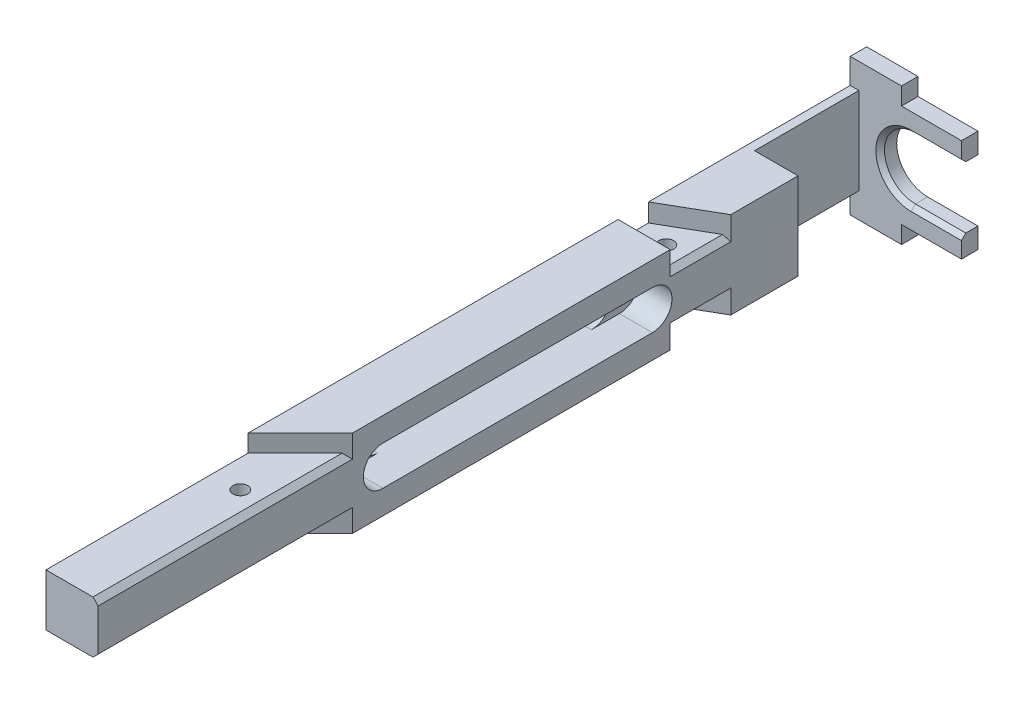
SolidWorks part; units mm, degrees
ref_plane "前视基准面" through (0, 0, 0) normal (0, 0, 1) x (1, 0, 0)
ref_plane "上视基准面" through (0, 0, 0) normal (0, 1, 0) x (1, 0, 0)
ref_plane "右视基准面" through (0, 0, 0) normal (1, 0, 0) x (0, 0, -1)
sketch "草图1" plane through (0, 0, 0) normal (1, 0, 0) x (0, 0, -1)
  line L0 (-15.5, 0) -> (15.5, 0) construction
  line L1 (-25, 5) -> (25, 5)
  line L2 (-25, 5) -> (-25, 3)
  line L3 (-25, -5) -> (25, -5)
  line L4 (25, 5) -> (25, 3)
  line L5 (-25, 5) -> (25, -5) construction
  line L6 (-25, -5) -> (25, 5) construction
  line L7 (-15.5, 2.25) -> (15.5, 2.25)
  line L8 (-15.5, -2.25) -> (15.5, -2.25)
  line L9 (-12.3, 0) -> (12.3, 0) construction
  line L10 (-12.3, 2.25) -> (12.3, 2.25)
  line L11 (-12.3, -2.25) -> (12.3, -2.25)
  line L12 (25, 3) -> (48.25, 3)
  line L13 (-48.25, 3) -> (-25, 3)
  line L14 (-48.25, 3) -> (-48.25, -3)
  line L15 (-48.25, -3) -> (-25, -3)
  line L16 (48.25, 3) -> (48.25, -3)
  line L17 (-48.25, 3) -> (48.25, -3) construction
  line L18 (-48.25, -3) -> (48.25, 3) construction
  line L19 (25, -3) -> (48.25, -3)
  line L20 (-25, -3) -> (-25, -5)
  line L21 (25, -3) -> (25, -5)
  arc A0 (-15.5, 2.25) -> (-15.5, -2.25) centre (-15.5, 0) ccw
  arc A1 (15.5, -2.25) -> (15.5, 2.25) centre (15.5, 0) ccw
  arc A2 (-12.3, 2.25) -> (-12.3, -2.25) centre (-12.3, 0) ccw
  arc A3 (12.3, -2.25) -> (12.3, 2.25) centre (12.3, 0) ccw
  point P0 (0, 0)
  point P8 (0, 0)
  point P14 (0, 0)
  point P20 (0, 0)
  dimension "D1" = 31
  dimension "D2" = 24.6
  dimension "D3" = 4.5
  dimension "D4" = 10
  dimension "D5" = 23.25
  dimension "D6" = 96.5
  dimension "D7" = 6
extrude "凸台-拉伸1" add sketch "草图1" against normal blind 6 contours L2 L13 L14 L15 L20 L3 L21 L19 L16 L12 L4 L1
extrude "切除-拉伸1" cut sketch "草图1<3>" against normal blind 3.8 contours A0 L8 A1 L7
sketch "草图1<3>" plane through (0, 0, 0) normal (1, 0, 0) x (0, 0, -1) same geometry as "草图1"
extrude "切除-拉伸2" cut sketch "草图1<4>" against normal through all contours A2 L11 A3 L10
sketch "草图1<4>" plane through (0, 0, 0) normal (1, 0, 0) x (0, 0, -1) same geometry as "草图1"
sketch "草图3" plane through (0, 0, -48.25) normal (0, 0, -1) x (-1, 0, 0)
  line L1 (-7.6413, 9.5848) -> (10.8952, 9.5848)
  line L2 (-7.6413, 9.5848) -> (-7.6413, -6.0527)
  line L3 (-7.6413, -6.0527) -> (10.8952, -6.0527)
  line L4 (10.8952, 9.5848) -> (10.8952, -6.0527)
extrude "切除-拉伸3" cut sketch "草图3" against normal blind 4
sketch "草图4" plane through (0, 0, -25) normal (0, 0, -1) x (-1, 0, 0)
  line L1 (0, 5) -> (6, 5)
  line L2 (0, 5) -> (0, -5)
  line L3 (0, -5) -> (6, -5)
  line L4 (6, 5) -> (6, -5)
extrude "凸台-拉伸2" add sketch "草图4" along normal up to surface (19.25 mm away) up to face at (-3, 0, -44.25)
sketch "草图5" plane through (0, -5, 0) normal (0, -1, 0) x (1, 0, 0)
  circle A4 centre (-2.8, 29.1) radius 0.85
  circle A5 centre (-2.8, -19.9) radius 0.85
  circle A8 centre (-2.8, -19.9) radius 1.2 construction
  circle A9 centre (-2.8, 29.1) radius 1.2 construction
  dimension "D1" = 1.7
extrude "切除-拉伸4" cut sketch "草图5" against normal through all
sketch "草图7" plane through (0, 0, -44.25) normal (0, 0, -1) x (-1, 0, 0)
  line L0 (6, 5) -> (6, -5) construction
  line L1 (6, 5.9) -> (-6.8, 5.9)
  line L2 (6, 5.9) -> (6, -5.9)
  line L3 (6, -5.9) -> (-6.8, -5.9)
  line L4 (-6.8, 5.9) -> (-6.8, -5.9)
  line L5 (6, 5) -> (0, 5) construction
  line L6 (0, -5) -> (6, -5) construction
  dimension "D1" = 0.9
  dimension "D2" = 0.9
  dimension "D3" = 12.8
extrude "凸台-拉伸3" add sketch "草图7" along normal blind 1.9
sketch "草图8" plane through (0, 0, 0) normal (1, 0, 0) x (0, 0, -1)
  line L0 (-25, -5) -> (44.25, -5) construction
  line L1 (44.25, 5) -> (32.25, 5)
  line L2 (44.25, 5) -> (44.25, -5)
  line L3 (44.25, -5) -> (32.25, -5)
  line L4 (32.25, 5) -> (32.25, -5)
  dimension "D1" = 12
extrude "切除-拉伸5" cut sketch "草图8" against normal offset from surface (5 mm away) 1 up to face at (-6, 0, -6.0667)
sketch "草图9" plane through (0, 0, -44.25) normal (0, 0, 1) x (1, 0, 0)
  line L0 (12.6, 0) -> (1, 0) construction
  line L1 (6.8, 5.9) -> (6.8, -5.9) construction
  line L2 (12.6, -3.55) -> (1, -3.55)
  line L3 (12.6, 3.55) -> (1, 3.55)
  arc A0 (12.6, -3.55) -> (12.6, 3.55) centre (12.6, 0) ccw
  arc A1 (1, 3.55) -> (1, -3.55) centre (1, 0) ccw
  point P5 (6.8, 0)
  dimension "D1" = 11.6
  dimension "D2" = 7.1
extrude "切除-拉伸6" cut sketch "草图9" against normal blind 5
chamfer "倒角1" distance 0.5 angle 45 3 edges at (3.9, 3.55, -44.25) (3.9, -3.55, -44.25) (-2.55, 0, -44.25)
sketch "草图10" plane through (-6, 0, 0) normal (-1, 0, 0) x (0, 0, 1)
  line L1 (-46.15, 7.9) -> (-44.25, 7.9)
  line L2 (-46.15, 7.9) -> (-46.15, 5.9)
  line L3 (-46.15, -7.9) -> (-44.25, -7.9)
  line L4 (-44.25, 7.9) -> (-44.25, 5.9)
  line L5 (-52.3787, 0) -> (-37.6849, 0) construction
  line L6 (-46.15, 5.9) -> (-44.25, 5.9) construction
  line L7 (-46.15, -5.9) -> (-44.25, -5.9) construction
  line L8 (-46.15, -5.9) -> (-46.15, 5.9) construction
  line L9 (-44.25, -5.9) -> (-44.25, -5) construction
  line L10 (-46.15, -5.9) -> (-44.25, -5.9)
  line L11 (-46.15, 5.9) -> (-44.25, 5.9)
  line L12 (-46.15, -5.9) -> (-46.15, -7.9)
  line L13 (-44.25, -5.9) -> (-44.25, -7.9)
  dimension "D1" = 15.8
extrude "凸台-拉伸4" add sketch "草图10" against normal blind 5.9
chamfer "倒角2" distance 6 angle 45 2 edges at (0, 4, 25) (0, -4, 25)
sketch "草图11" plane through (0, 5, 0) normal (0, 1, 0) x (1, 0, 0)
  line L0 (0, 24.5141) -> (-6, 21.05)
  line L1 (0, -19) -> (0, 32.25) construction
  line L2 (-6, -25) -> (-6, 44.25) construction
  line L3 (-6, 21.05) -> (-6, 17.55)
  line L4 (-6, 17.55) -> (0, 17.55)
  line L5 (0, 17.55) -> (0, 24.5141)
  line L6 (-6, -48.25) -> (0, -48.25) construction
  dimension "D1" = 60
  dimension "D2" = 65.8
  dimension "D3" = 3.5
extrude "切除-拉伸7" cut sketch "草图11" against normal blind 2.1
extrude "切除-拉伸8" cut sketch "草图11<2>" along normal blind 2.1 from surface starting at face at (-3.6667, -5, -18.1667)
sketch "草图11<2>" plane through (0, 5, 0) normal (0, 1, 0) x (1, 0, 0) same geometry as "草图11"
chamfer "倒角3" distance 0.6 angle 45 4 edges at (0, -3, 33.625) (0, 3, 33.625) (0, -2.9, -21.0321) (0, 2.9, -21.0321)
